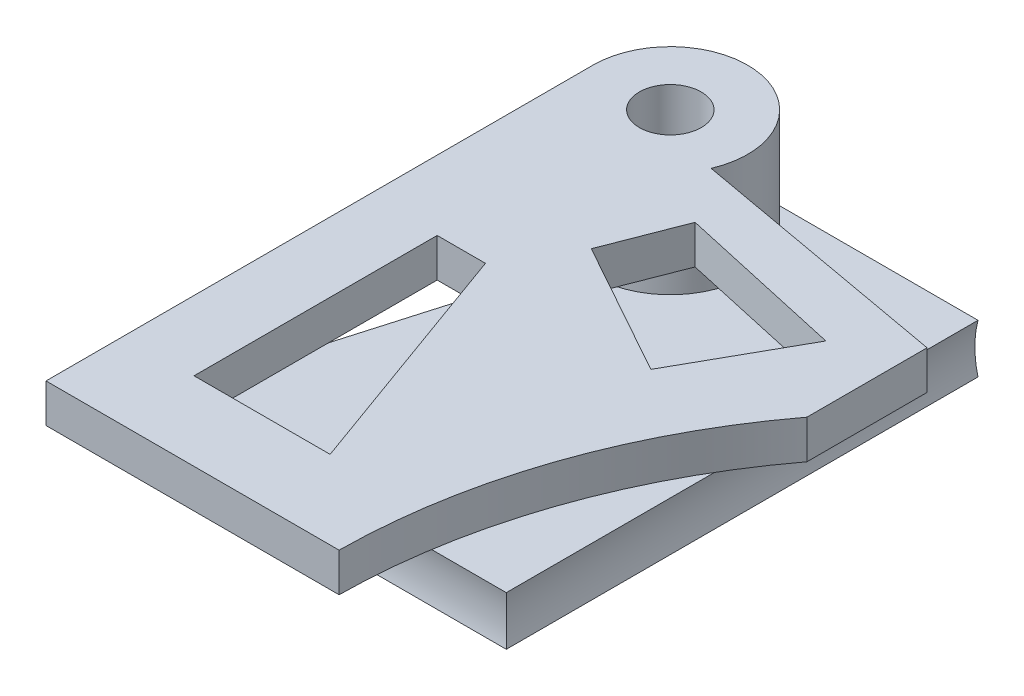
SolidWorks part; units mm, degrees
ref_plane "Front Plane" through (0, 0, 0) normal (0, 0, 1) x (1, 0, 0)
ref_plane "Top Plane" through (0, 0, 0) normal (0, 1, 0) x (1, 0, 0)
ref_plane "Right Plane" through (0, 0, 0) normal (1, 0, 0) x (0, 0, -1)
sketch "Sketch1" plane through (0, 0, 0) normal (0, 1, 0) x (1, 0, 0)
  line L6 (30.8201, 39.1183) -> (30.8201, -21.8817)
  line L8 (30.8201, -21.8817) -> (-13.4276, -21.8817)
  line L9 (42.9102, -21.8817) -> (-457.0898, -21.8817) construction
  line L10 (-13.4276, -21.8817) -> (-1.4417, 19.4529)
  line L13 (30.8201, 39.1183) -> (1.7979, 39.1183)
  circle A0 centre (1, 29.1502) radius 4
  circle A1 centre (1, 29.1502) radius 10
  dimension "D2" = 20
  dimension "D3" = 8
  dimension "D1" = 61
extrude "Boss-Extrude1" add sketch "Sketch1" along normal blind 6.35 contours A1 region at (13.3067, 0, -4.4571)
extrude "Boss-Extrude2" add sketch "Sketch1<3>" along normal blind 20 contours A1 A0 | A1 A0 region at (8.1399, 0, -35.7414)
sketch "Sketch1<3>" plane through (0, 0, 0) normal (0, 1, 0) x (1, 0, 0) same geometry as "Sketch1"
ref_plane "Plane1" through (0, 10, 0) normal (0, 1, 0) x (1, 0, 0)
sketch "Sketch3" plane through (0, 0, 0) normal (0, 0, 1) x (1, 0, 0)
  line L0 (30.8201, 3.175) -> (121.9702, 3.175) construction
  line L1 (30.8201, 6.35) -> (30.8201, 0) construction
  circle A0 centre (42.9102, 3.175) radius 12.5
  dimension "D1" = 25
extrude "Cut-Extrude1" cut sketch "Sketch3" against normal through all both and the other way through all
sketch "Sketch4" plane through (0, 0, 0) normal (1, 0, 0) x (0, 0, -1)
  line L0 (-35.1146, 3.175) -> (-60.5591, 3.175) construction
  circle A0 centre (-33.9717, 3.175) radius 12.5
  point P2 (-46.5637, 3.0826)
  point P7 (-39.6376, 3.175)
  dimension "D1" = 25
extrude "Cut-Extrude3" cut sketch "Sketch4" along normal through all both and the other way through all
sketch "Sketch5" plane through (0, 20, 0) normal (0, 1, 0) x (1, 0, 0)
  line L0 (-9, 29.1502) -> (-9, -41.5829)
  line L5 (0, -31.4363) -> (0, 0)
  line L6 (10.1991, 25.229) -> (57.0219, 16.7954)
  line L7 (-9, -41.5829) -> (28.9004, -41.5829)
  line L8 (44.2561, 19.0948) -> (44.2561, 3.5588)
  line L9 (0, 0) -> (6.2423, 0)
  line L12 (17.595, -31.4363) -> (0, -31.4363)
  line L13 (11.4551, 8.4817) -> (15.2018, 18.1471)
  line L14 (15.2018, 18.1471) -> (36.949, 13.3144)
  line L15 (36.949, 13.3144) -> (28.816, -1.1837)
  line L16 (28.816, -1.1837) -> (11.4551, 8.4817)
  line L17 (6.2423, 0) -> (17.595, -31.4363)
  circle A0 centre (1, 29.1502) radius 10 construction
  circle A1 centre (1, 29.1502) radius 4
  circle A2 centre (1, 29.1502) radius 10
  arc A4 (57.0219, 16.7954) -> (28.9004, -41.5829) centre (105.0586, -42.3067) ccw
  circle M6 centre (1, 29.1502) radius 10
extrude "Boss-Extrude3" add sketch "Sketch5" against normal blind 5 contours M6 region at (14.3319, 20, 7.8592)
